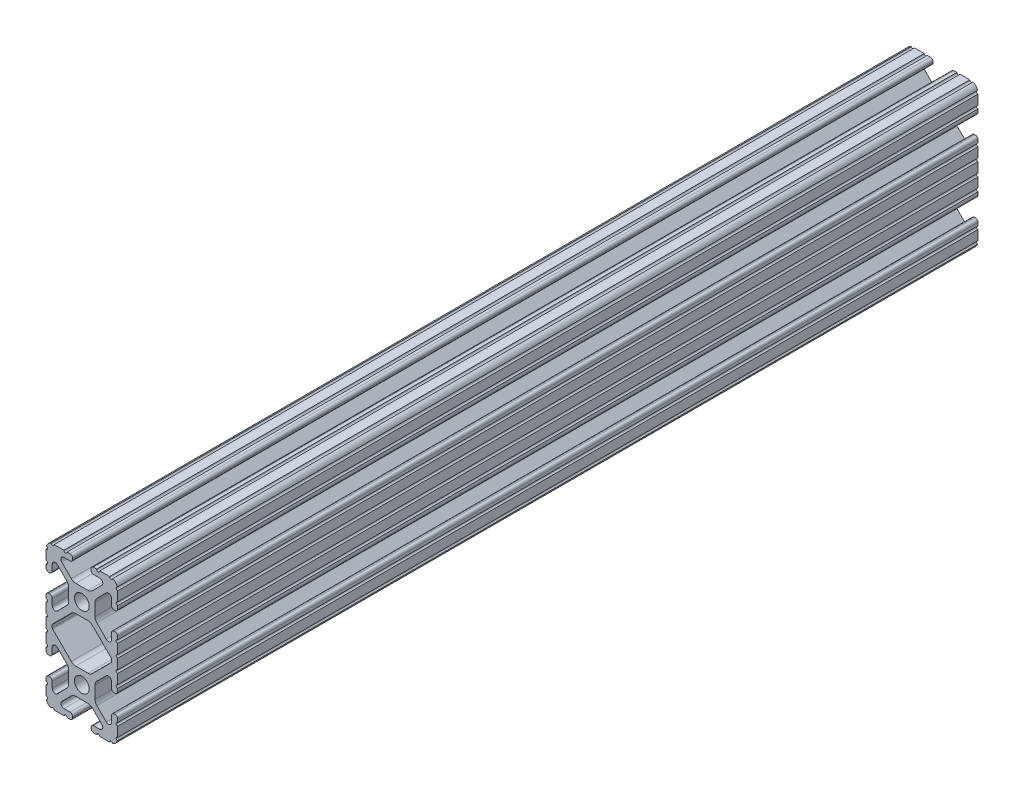
SolidWorks part; units mm, degrees
ref_plane "Front Plane" through (0, 0, 0) normal (0, 0, 1) x (1, 0, 0)
ref_plane "Top Plane" through (0, 0, 0) normal (0, 1, 0) x (1, 0, 0)
ref_plane "Right Plane" through (0, 0, 0) normal (1, 0, 0) x (0, 0, -1)
sketch "Sketch2" plane through (0, 0, 0) normal (0, 0, 1) x (1, 0, 0)
  line L0 (0, 25.4) -> (0, -25.4) construction
  line L1 (-12.7, 0) -> (12.7, 0) construction
  line L2 (3.2512, -25.4) -> (12.7, -25.4)
  line L3 (12.7, -25.4) -> (12.7, -15.9512)
  line L4 (3.2512, -25.4) -> (3.2512, -23.1902)
  line L5 (3.2512, -23.1902) -> (8.9276, -23.1902)
  line L6 (8.9276, -23.1902) -> (3.0856, -17.3482)
  line L7 (0, -12.7) -> (12.7, -25.4) construction
  line L8 (12.7, -15.9512) -> (10.4902, -15.9512)
  line L9 (10.4902, -15.9512) -> (10.4902, -21.6276)
  line L10 (10.4902, -21.6276) -> (4.6482, -15.7856)
  line L11 (3.2512, -25.4) -> (0, -25.4) construction
  line L12 (0, -25.4) -> (-3.2512, -25.4) construction
  line L13 (-3.2512, -25.4) -> (-12.7, -25.4) construction
  line L14 (12.7, 25.4) -> (-12.7, 25.4) construction
  line L15 (0, 12.7) -> (0, -12.7) construction
  circle A0 centre (0, -12.7) radius 2.6035
  arc A1 (6.3485, -23.1902) -> (7.1039, -21.3665) centre (6.3485, -22.1219) ccw construction
  point P8 (0, -17.3482)
  point P16 (-2.6035, -12.7)
  point P18 (2.6035, -12.7)
  point P19 (0, -10.0965)
  point P20 (0, -15.3035)
  point P27 (-12.7, -25.4)
  point P30 (0, 25.4)
  point P31 (12.7, 25.4)
  point P32 (-12.7, 25.4)
  point P33 (12.7, -25.4)
  point P34 (0, -12.7)
  point P35 (0, 12.7)
  point P37 (0, 0)
  point P38 (-3.2512, -25.4)
  point P39 (3.2512, -25.4)
  dimension "Center Hole Diameter" = 5.207
  dimension "Rail Height" = 50.8
  dimension "Rail Width" = 25.4
  dimension "T-Slot Width" = 6.5024
  dimension "Slot Inner Width" = 14.8336
  dimension "Thickness" = 2.2098
  dimension "Slot Depth" = 5.842
  dimension "D1" = 2.2098
  dimension "C to C" = 25.4
sketch "Sketch3" plane through (0, 0, 0) normal (1, 0, 0) x (0, 0, -1)
  line L0 (-152.4, -25.4) -> (152.4, -25.4) construction
  line L1 (-101.6, 0) -> (101.6, 0) construction
  point P6 (-152.4, -25.4)
  point P8 (-101.6, 0)
  point P9 (101.6, 0)
  point P10 (152.4, -25.4)
  dimension "Length" = 304.8
sketch "Sketch4" plane through (0, 0, 0) normal (0, 0, 1) x (1, 0, 0)
  line L0 (4.1904, -25.4) -> (10.1173, -25.4)
  line L1 (3.2512, -25.4) -> (12.7, -25.4) construction
  line L2 (3.2512, -25.4) -> (3.2512, -23.1902) construction
  line L3 (3.2512, -23.1902) -> (8.9276, -23.1902) construction
  line L4 (3.2512, -24.1294) -> (3.2512, -24.4608)
  line L5 (4.1904, -23.1902) -> (6.3485, -23.1902)
  line L6 (0, -17.3482) -> (2.164, -17.3482)
  line L7 (8.9276, -23.1902) -> (3.0856, -17.3482) construction
  line L8 (3.7373, -17.9999) -> (7.1039, -21.3665)
  line L9 (12.7, -25.4) -> (12.7, -15.9512) construction
  line L10 (10.4902, -21.6276) -> (4.6482, -15.7856) construction
  line L11 (10.4902, -15.9512) -> (10.4902, -21.6276) construction
  line L12 (10.4902, -19.0485) -> (10.4902, -16.8904)
  line L13 (12.7, -15.9512) -> (10.4902, -15.9512) construction
  line L14 (11.4294, -15.9512) -> (11.7608, -15.9512)
  line L15 (12.7, -16.8904) -> (12.7, -22.8173)
  line L16 (8.6665, -19.8039) -> (5.2999, -16.4373)
  line L17 (4.6482, -12.7) -> (4.6482, -14.864)
  line L19 (0, -17.3482) -> (0, -15.3035)
  line L20 (0, 25.4) -> (0, -25.4) construction
  line L21 (4.6482, -12.7) -> (2.6035, -12.7)
  arc A0 (3.2512, -24.4608) -> (4.1904, -25.4) centre (4.1904, -24.4608) ccw
  circle A1 centre (0, -12.7) radius 2.6035 construction
  arc A2 (3.2512, -24.1294) -> (4.1904, -23.1902) centre (4.1904, -24.1294) cw
  arc A3 (6.3485, -23.1902) -> (7.1039, -21.3665) centre (6.3485, -22.1219) ccw
  arc A4 (2.164, -17.3482) -> (3.7373, -17.9999) centre (2.164, -19.5732) cw
  arc A5 (10.1173, -25.4) -> (12.7, -22.8173) centre (10.1173, -22.8173) ccw
  arc A6 (8.6665, -19.8039) -> (10.4902, -19.0485) centre (9.4219, -19.0485) ccw
  arc A7 (10.4902, -16.8904) -> (11.4294, -15.9512) centre (11.4294, -16.8904) cw
  arc A8 (11.7608, -15.9512) -> (12.7, -16.8904) centre (11.7608, -16.8904) cw
  arc A9 (5.2999, -16.4373) -> (4.6482, -14.864) centre (6.8732, -14.864) cw
  arc A11 (0, -15.3035) -> (2.6035, -12.7) centre (0, -12.7) ccw
  dimension "D1" = 2.5827
  dimension "D2" = 2.225
  dimension "D3" = 0.9392
extrude "Boss-Extrude1" add sketch "Sketch4" along normal mid plane 304.8
sketch "Sketch5" plane through (0, 0, 0) normal (0, 0, 1) x (1, 0, 0)
  line L0 (3.2512, -25.4) -> (12.7, -25.4) construction
  line L1 (4.1904, -23.1902) -> (6.3485, -23.1902) construction
  line L3 (0, -12.7) -> (12.7, -25.4) construction
  line L4 (6.3485, -23.1902) -> (6.3485, -25.4) construction
  line L5 (8.9276, -23.1902) -> (3.0856, -17.3482) construction
  circle A0 centre (10.3562, -25.4) radius 0.5524
  circle A1 centre (5.796, -25.4) radius 0.5524
  circle A2 centre (12.7, -23.0562) radius 0.5524
  circle A3 centre (12.7, -18.496) radius 0.5524
  point P10 (5.2694, -23.1902)
  point P12 (9.4219, -19.0485)
  dimension "D1" = 1.1049
extrude "Cut-Extrude1" cut sketch "Sketch5" against normal through all both and the other way through all
mirror "Mirror1" about plane through (4.6482, -12.7, 152.4) normal (0, -1, 0) of bodies 137 134
sketch "Sketch6" plane through (0, 0, 0) normal (0, 0, 1) x (1, 0, 0)
  line L0 (12.7, -1.7914) -> (12.7, 0)
  line L1 (12.7, 0) -> (9.8037, 0)
  line L2 (-12.7, 0) -> (12.7, 0) construction
  line L3 (9.8037, 0) -> (9.8037, -2.3438)
  line L4 (9.8037, -2.3438) -> (12.1476, -2.3438)
  circle A0 centre (12.7, -2.3438) radius 0.5524 construction
  arc A1 (12.7, -1.7914) -> (12.1476, -2.3438) centre (12.7, -2.3438) ccw
  arc A4 (12.58, -1.8046) -> (12.7, -2.8963) centre (12.7, -2.3438) ccw construction
  arc A6 (9.8037, 0) -> (10.8954, -0.12) centre (10.3562, 0) ccw construction
extrude "Boss-Extrude2" add sketch "Sketch6" along normal mid plane 304.8
sketch "Sketch7" plane through (0, 0, 0) normal (0, 0, 1) x (1, 0, 0)
  line L0 (5.4206, -5.7168) -> (10.3284, -0.809)
  line L1 (3.7373, -7.4001) -> (7.1039, -4.0335) construction
  line L2 (10.4902, -0.4184) -> (10.4902, 0)
  line L3 (0, 0) -> (10.4902, 0)
  line L4 (-12.7, 0) -> (12.7, 0) construction
  line L5 (0, 0) -> (5.4206, -5.7168)
  arc A0 (10.3284, -0.809) -> (10.4902, -0.4184) centre (9.9377, -0.4184) ccw
  arc A3 (12.7, -1.7914) -> (12.7, -2.8963) centre (12.7, -2.3438) ccw construction
extrude "Cut-Extrude2" cut sketch "Sketch7" against normal through all both and the other way through all
mirror "Mirror2" about plane through (0, 0, 0) normal (0, 1, 0) of bodies 139 135
mirror "Mirror3" about plane through (0, 0, 0) normal (1, 0, 0) of bodies 136
equation "\"D1@Boss-Extrude1\"=\"Length@Sketch3\""
equation "\"D1@Sketch2\"=\"Thickness@Sketch2\""
equation "\"D2@Sketch4\"=\"Slot Inner Width@Sketch2\"*0.15"
equation "\"D1@Sketch4\"=\"D3@Sketch4\"*2.75"
equation "\"D3@Sketch4\"=\"Thickness@Sketch2\"*0.425"
equation "\"D1@Sketch5\"=\"Thickness@Sketch2\"*0.5"
equation "\"D1@Boss-Extrude2\"=\"Length@Sketch3\""
